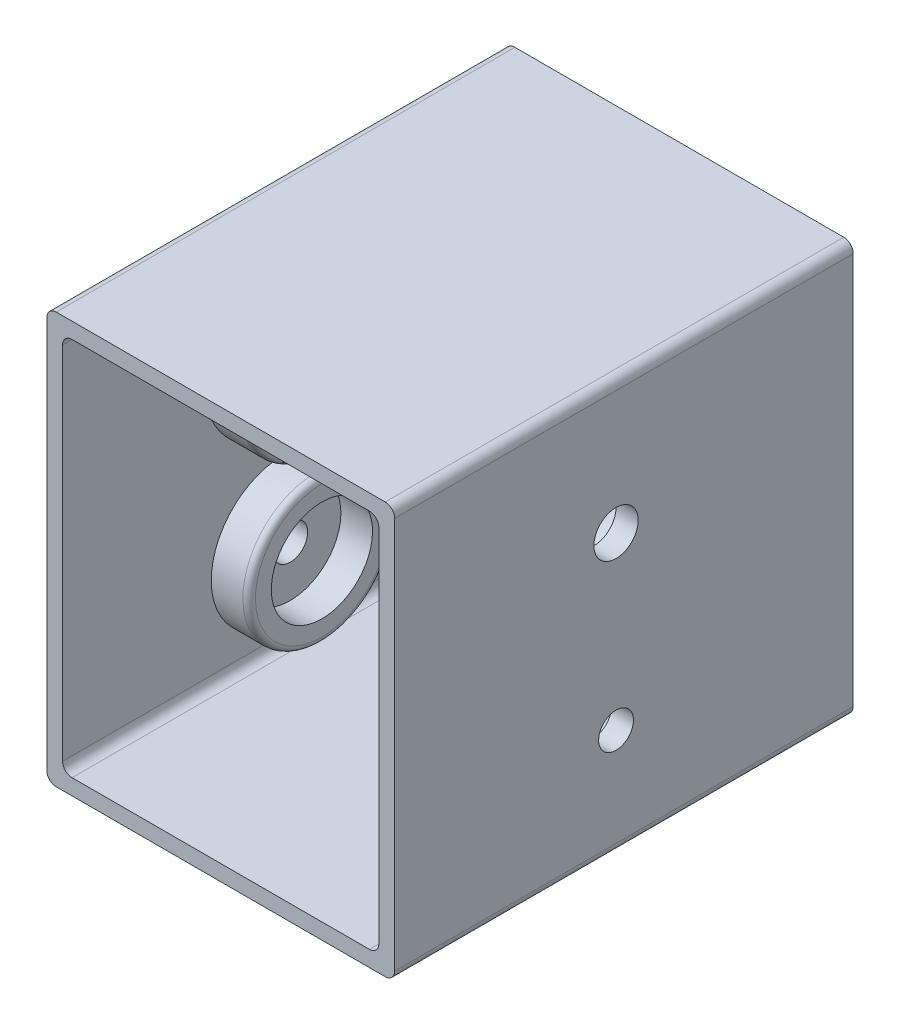
SolidWorks part; units mm, degrees
material "6061 Alloy"
ref_plane "Front Plane" through (0, 0, 0) normal (1, 0, 0) x (0, 1, 0)
ref_plane "Top Plane" through (0, 0, 0) normal (0, 0, 1) x (0, 1, 0)
ref_plane "Right Plane" through (0, 0, 0) normal (0, 1, 0) x (-1, 0, 0)
sketch "Sketch1" plane through (0, 0, 0) normal (0, 0, 1) x (0, 1, 0)
  line L1 (65, 55) -> (-65, 55)
  line L2 (65, 55) -> (65, -55)
  line L3 (65, -55) -> (-65, -55)
  line L4 (-65, 55) -> (-65, -55)
  line L5 (65, 55) -> (-65, -55) construction
  line L6 (65, -55) -> (-65, 55) construction
  point P0 (0, 0)
  dimension "D1" = 110
  dimension "D2" = 130
extrude "Boss-Extrude1" add sketch "Sketch1" along normal blind 145
shell "Shell2" thickness 5 removed face at (0, 0, 145)
sketch "Sketch2" plane through (-50, 0, 0) normal (1, 0, 0) x (0, 1, 0)
  line L0 (-65, 145) -> (-65, 0) construction
  circle A0 centre (-31, 75) radius 23
  circle A1 centre (23, 75) radius 25
  dimension "D1" = 46
  dimension "D2" = 50
  dimension "D3" = 75
  dimension "D4" = 34
  dimension "D5" = 88
  dimension "D6" = 75
extrude "Boss-Extrude2" add sketch "Sketch2" along normal blind 12 contours A0 region at (-50, -31, 75)
extrude "Boss-Extrude3" add sketch "Sketch2<3>" along normal blind 13 contours A1 region at (-50, 23, 75)
sketch "Sketch2<3>" plane through (-50, 0, 0) normal (1, 0, 0) x (0, 1, 0) same geometry as "Sketch2"
ref_plane "Plane1" through (0, 0, 0) normal (1, 0, 0) x (0, 1, 0)
sketch "Sketch3" plane through (-38, 0, 0) normal (1, 0, 0) x (0, 1, 0)
  line L0 (-65, 0) -> (65, 0) construction
  line L1 (-65, 145) -> (-65, 0) construction
  circle A0 centre (-31, 75) radius 16
  dimension "D2" = 32
  dimension "D1" = 75
  dimension "D5" = 34
extrude "Cut-Extrude1" cut sketch "Sketch3" against normal blind 10 contours A0
sketch "Sketch4" plane through (-37, 0, 0) normal (1, 0, 0) x (0, 1, 0)
  line L1 (-65, 145) -> (-65, 0) construction
  circle A0 centre (23, 75) radius 17.5
  dimension "D1" = 35
  dimension "D2" = 88
  dimension "D3" = 75
extrude "Cut-Extrude4" cut sketch "Sketch4" against normal blind 11
mirror "Mirror1" about plane through (0, 0, 0) normal (1, 0, 0) of "Cut-Extrude4", "Cut-Extrude1", "Boss-Extrude3", "Boss-Extrude2"
sketch "Sketch5" plane through (-55, 0, 0) normal (-1, 0, 0) x (0, -1, 0)
  line L0 (65, 145) -> (65, 0) construction
  circle A0 centre (31, 75) radius 5.5
  circle A1 centre (-23, 75) radius 7
  dimension "D5" = 14
  dimension "D6" = 11
  dimension "D1" = 75
  dimension "D2" = 75
  dimension "D3" = 34
  dimension "D4" = 88
extrude "Cut-Extrude5" cut sketch "Sketch5" against normal through all
sketch "Sketch7" plane through (0, 0, 0) normal (0, 0, -1) x (1, 0, 0)
  line L0 (-55, -65) -> (-55, 65) construction
  line L1 (-55, 65) -> (55, 65) construction
  circle A0 centre (-40, 50) radius 4.25
  circle A1 centre (40, 50) radius 4.25
  circle A2 centre (-40, -50) radius 4.25
  circle A3 centre (40, -50) radius 4.25
  dimension "D1" = 8.5
  dimension "D2" = 8.5
  dimension "D3" = 8.5
  dimension "D4" = 8.5
  dimension "D5" = 15
  dimension "D6" = 95
  dimension "D7" = 115
  dimension "D8" = 15
  dimension "D9" = 115
  dimension "D10" = 15
  dimension "D11" = 15
  dimension "D12" = 95
extrude "Cut-Extrude6" cut sketch "Sketch7" against normal blind 10
fillet "Fillet1" radius 3 8 edges at (-55, 65, 72.5) (55, 65, 72.5) (55, -65, 72.5) (-55, -65, 72.5) (50, 60, 77.5) (50, -60, 77.5) (-50, -60, 77.5) (-50, 60, 77.5)
fillet "Fillet2" radius 2 4 edges at (38, -8, 75) (37, 48, 75) (-38, -8, 75) (-37, 48, 75)
